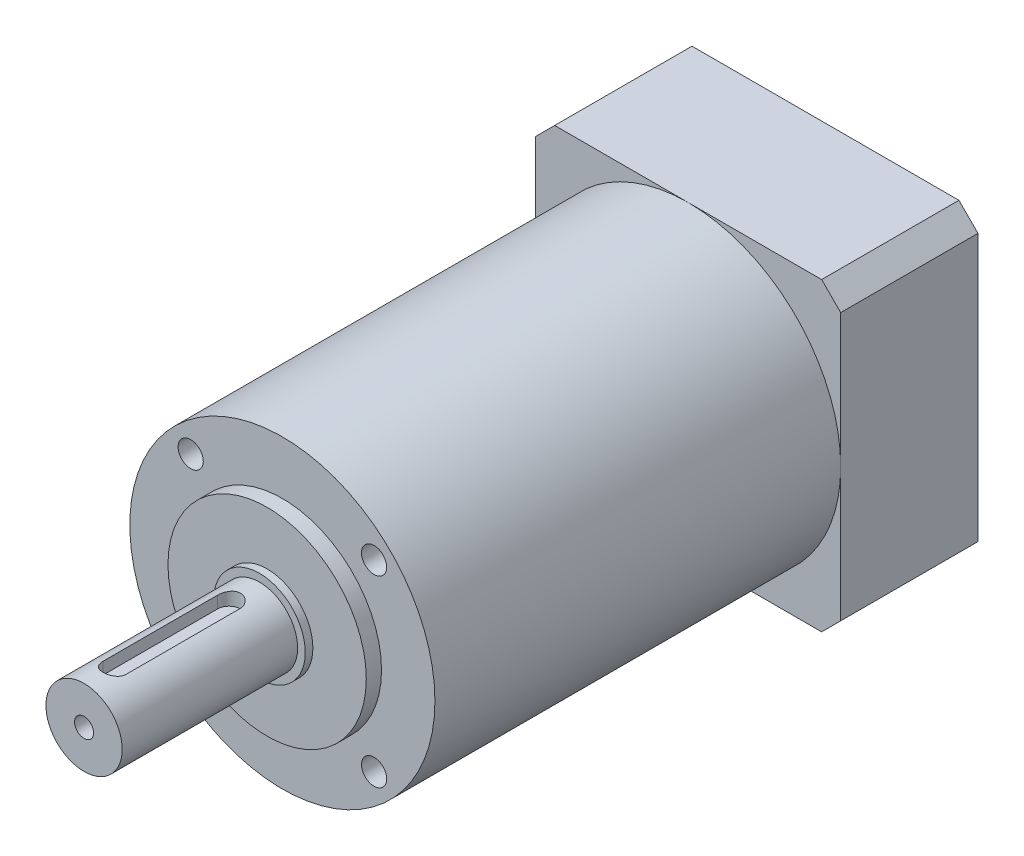
SolidWorks part; units mm, degrees
ref_plane "Front" through (0, 0, 0) normal (0, 0, 1) x (1, 0, 0)
ref_plane "Top" through (0, 0, 0) normal (0, 1, 0) x (1, 0, 0)
ref_plane "Right" through (0, 0, 0) normal (1, 0, 0) x (0, 0, -1)
sketch "Эскиз1" plane through (0, 0, 0) normal (0, 0, 1) x (1, 0, 0)
  line L1 (0, 0) -> (40, 0)
  line L2 (0, 0) -> (0, 40)
  line L3 (0, 40) -> (40, 40)
  line L4 (40, 0) -> (40, 40)
  dimension "D1" = 40
  dimension "D2" = 40
extrude "Бобышка-Вытянуть1" add sketch "Эскиз1" along normal blind 18
sketch "Эскиз2" plane through (0, 0, 18) normal (0, 0, 1) x (1, 0, 0)
  line L1 (0, 0) -> (40, 0) construction
  line L2 (40, 0) -> (40, 40) construction
  circle A0 centre (20, 20) radius 20
  dimension "D1" = 40
extrude "Бобышка-Вытянуть2" add sketch "Эскиз2" along normal blind 53.2
sketch "Эскиз3" plane through (0, 0, 71.2) normal (0, 0, 1) x (1, 0, 0)
  circle A0 centre (20, 20) radius 13
  arc A1 (40, 20) -> (20, 40) centre (20, 20) ccw construction
  dimension "D1" = 26
extrude "Бобышка-Вытянуть3" add sketch "Эскиз3" along normal blind 2
sketch "Эскиз4" plane through (0, 0, 73.2) normal (0, 0, 1) x (1, 0, 0)
  circle A0 centre (20, 20) radius 6
  circle A1 centre (20, 20) radius 13 construction
  dimension "D1" = 12
extrude "Бобышка-Вытянуть4" add sketch "Эскиз4" along normal blind 1
sketch "Эскиз5" plane through (0, 0, 74.2) normal (0, 0, 1) x (1, 0, 0)
  circle A0 centre (20, 20) radius 5
  circle A1 centre (20, 20) radius 6 construction
  dimension "D1" = 10
extrude "Бобышка-Вытянуть5" add sketch "Эскиз5" along normal blind 23 contours A0
ref_plane "Плоскость3" through (0, 25, 0) normal (0, -1, 0) x (-1, 0, 0)
sketch "Эскиз9" plane through (0, 25, 0) normal (0, -1, 0) x (-1, 0, 0)
  line L0 (-20, -93.2) -> (-20, -78.2) construction
  line L1 (-21.5, -93.2) -> (-21.5, -78.2)
  line L2 (-18.5, -93.2) -> (-18.5, -78.2)
  line L3 (-25, -97.2) -> (-15, -97.2) construction
  arc A0 (-21.5, -93.2) -> (-18.5, -93.2) centre (-20, -93.2) ccw
  arc A1 (-18.5, -78.2) -> (-21.5, -78.2) centre (-20, -78.2) ccw
  point P2 (-20, -85.7)
  dimension "D2" = 1.5
  dimension "D1" = 15
  dimension "D3" = 4
  dimension "D4" = 20
extrude "Вырез-Вытянуть1" cut sketch "Эскиз9" along normal blind 1.8
hole_wizard "Отверстие обработанное метчиком M31" positions "Эскиз11" profile "Эскиз10" tap size "M3" standard "DIN"
sketch "Эскиз11" plane through (0, 0, 97.2) normal (0, 0, 1) x (1, 0, 0)
  circle A0 centre (20, 20) radius 6 construction
  point P0 (20, 20)
sketch "Эскиз10" plane through (20, 20, 97.2) normal (1, 0, 0) x (0, -1, 0)
  line L0 (0, 0) -> (0, 15.7511)
  line L1 (0, 15.7511) -> (1.25, 15)
  line L2 (1.25, 15) -> (1.25, 0)
  line L5 (1.25, 0) -> (0, 0)
  line L10 (0, 15.7511) -> (-1.25, 15) construction
  line L11 (0, -6.35) -> (0, 107.95) construction
  dimension "Диаметр сверла" = 2.5
  dimension "Глубина сверла" = 15
  dimension "Угол заточки сверла" = 118
cosmetic thread "Отверстие резьбы1" parameters "D1"=10, "D2"=3
sketch "Эскиз12" plane through (0, 0, 71.2) normal (0, 0, 1) x (1, 0, 0)
  line L0 (7.9792, 32.0208) -> (20, 20)
  line L1 (20, 20) -> (3, 20)
  circle A0 centre (20, 20) radius 17
  point P3 (7.9792, 32.0208)
  dimension "D1" = 34
  dimension "D2" = 45
hole_wizard "Отверстие обработанное метчиком M41" positions "Эскиз13" profile "Эскиз14" tap size "M4" standard "DIN"
sketch "Эскиз13" plane through (0, 0, 71.2) normal (0, 0, 1) x (1, 0, 0)
  point P0 (7.9792, 32.0208)
sketch "Эскиз14" plane through (7.9792, 32.0208, 71.2) normal (1, 0, 0) x (0, -1, 0)
  line L0 (0, 0) -> (0, 7.9914)
  line L1 (0, 7.9914) -> (1.65, 7)
  line L2 (1.65, 7) -> (1.65, 0)
  line L5 (1.65, 0) -> (0, 0)
  line L10 (0, 7.9914) -> (-1.65, 7) construction
  line L11 (0, -6.35) -> (0, 107.95) construction
  dimension "Диаметр сверла" = 3.3
  dimension "Глубина сверла" = 7
  dimension "Угол заточки сверла" = 118
cosmetic thread "Отверстие резьбы2" parameters "D1"=7, "D2"=4
pattern_circular "Круговой массив1" count 4 over 360 about axis through (20, 20, 71.2) along (0, 0, 1) of "Отверстие обработанное метчиком M41"
cosmetic thread "Отверстие резьбы3" parameters "D1"=7, "D2"=4
cosmetic thread "Отверстие резьбы4" parameters "D1"=7, "D2"=4
cosmetic thread "Отверстие резьбы5" parameters "D1"=7, "D2"=4
chamfer "Фаска1" distance 2.5 angle 45 4 edges at (0, 0, 9) (40, 0, 9) (40, 40, 9) (0, 40, 9)
sketch "Эскиз15" plane through (0, 0, 0) normal (0, 0, -1) x (-1, 0, 0)
  circle A0 centre (-20, 20) radius 16.5
  dimension "D3" = 33
  dimension "D1" = 20
  dimension "D2" = 20
extrude "Вырез-Вытянуть2" cut sketch "Эскиз15" against normal blind 18
sketch "Эскиз16" plane through (0, 0, 18) normal (0, 0, -1) x (-1, 0, 0)
  line L3 (-21, 14.5917) -> (-21, 11.0557)
  line L5 (-19, 14.5917) -> (-19, 11.0557)
  arc A0 (-19, 14.5917) -> (-21, 14.5917) centre (-20, 20) ccw
  arc A1 (-19, 11.0557) -> (-21, 11.0557) centre (-20, 20) ccw
  dimension "D1" = 11
  dimension "D2" = 18
  dimension "D3" = 20
  dimension "D4" = 20
  dimension "D5" = 2
  dimension "D6" = 19
extrude "Бобышка-Вытянуть6" add sketch "Эскиз16" along normal blind 15
fillet "Скругление1" radius 0.5 2 edges at (20, 25.5, 3) (20, 29, 3)
sketch "Эскиз17" plane through (0, 0, 18) normal (0, 0, -1) x (-1, 0, 0)
  circle A0 centre (-20, 20) radius 9
  circle A1 centre (-20, 20) radius 13.5
  dimension "D1" = 27
  dimension "D2" = 18
extrude "Бобышка-Вытянуть7" add sketch "Эскиз17" along normal blind 16
fillet "Скругление2" radius 0.5 1 edges at (11, 20, 2)
sketch "Эскиз18" plane through (0, 0, 0) normal (0, 0, -1) x (-1, 0, 0)
  line L0 (-38.75, 38.75) -> (-1.25, 1.25)
  line L1 (-37.5, 40) -> (-40, 37.5) construction
  line L2 (-2.5, 0) -> (0, 2.5) construction
  line L3 (-1.25, 1.25) -> (-38.75, 1.25)
  line L4 (-40, 2.5) -> (-37.5, 0) construction
  line L5 (-38.75, 1.25) -> (-1.25, 38.75)
  line L6 (0, 37.5) -> (-2.5, 40) construction
  circle A0 centre (-20, 20) radius 22
  point P15 (-4.4437, 35.5563)
  dimension "D1" = 44
hole_wizard "Отверстие обработанное метчиком M42" positions "Эскиз19" profile "Эскиз20" tap size "M4" standard "DIN"
sketch "Эскиз19" plane through (0, 0, 0) normal (0, 0, -1) x (-1, 0, 0)
  point P14 (-4.4448, 35.5552)
sketch "Эскиз20" plane through (4.4448, 35.5552, 0) normal (1, 0, 0) x (0, 1, 0)
  line L0 (0, 0) -> (0, 11.4914)
  line L1 (0, 11.4914) -> (1.65, 10.5)
  line L2 (1.65, 10.5) -> (1.65, 0)
  line L5 (1.65, 0) -> (0, 0)
  line L10 (0, 11.4914) -> (-1.65, 10.5) construction
  line L11 (0, -6.35) -> (0, 107.95) construction
  dimension "Диаметр сверла" = 3.3
  dimension "Глубина сверла" = 10.5
  dimension "Угол заточки сверла" = 118
cosmetic thread "Отверстие резьбы6" parameters "D1"=7, "D2"=4
pattern_circular "Круговой массив2" count 4 over 360 about axis through (20, 20, 18) along (0, 0, -1) of "Отверстие обработанное метчиком M42"
cosmetic thread "Отверстие резьбы7" parameters "D1"=7, "D2"=4
cosmetic thread "Отверстие резьбы8" parameters "D1"=7, "D2"=4
cosmetic thread "Отверстие резьбы9" parameters "D1"=7, "D2"=4
